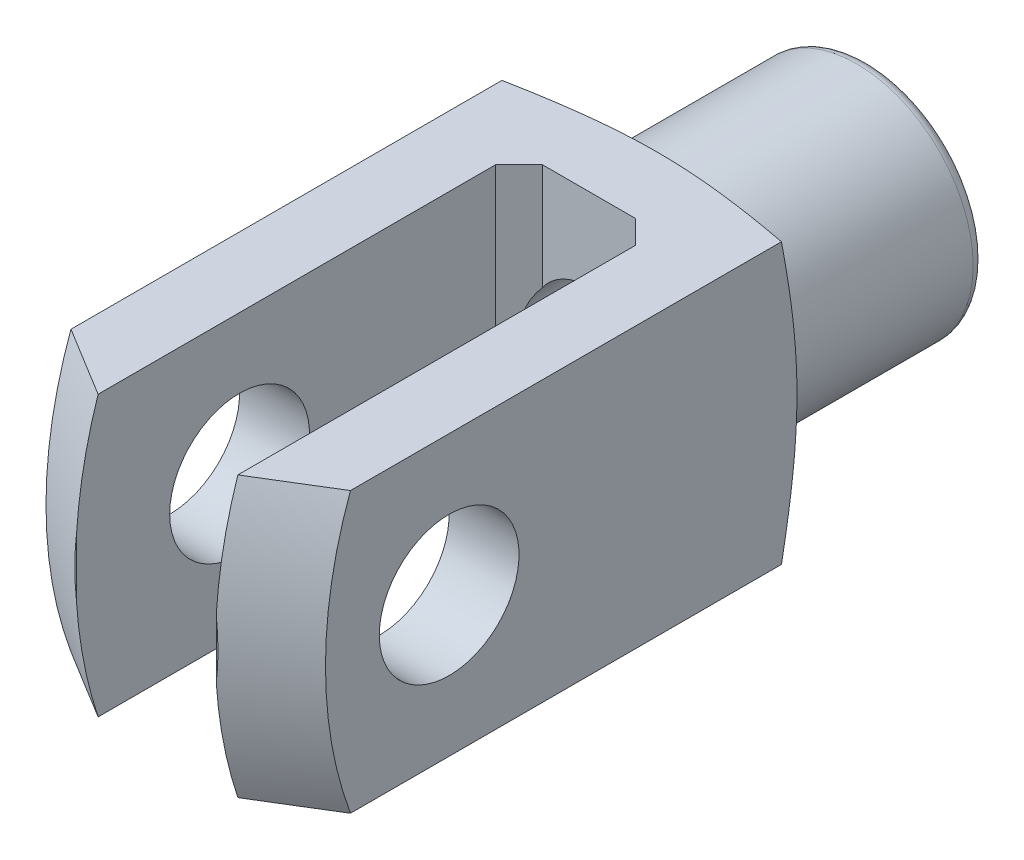
SolidWorks part; units mm, degrees
ref_plane "Front Plane" through (0, 0, 0) normal (0, 0, 1) x (1, 0, 0)
ref_plane "Top Plane" through (0, 0, 0) normal (0, 1, 0) x (1, 0, 0)
ref_plane "Right Plane" through (0, 0, 0) normal (1, 0, 0) x (0, 0, -1)
ref_plane "Plane1" through (0, 0, 0) normal (1, 0, 0) x (0, 0, -1)
sketch "Sketch1" plane through (0, 0, 0) normal (1, 0, 0) x (0, 0, -1)
  line L0 (-7, 0) -> (-7, 12)
  line L1 (-7, 12) -> (13.3253, 12)
  line L2 (13.3253, 12) -> (15, 5.75)
  line L3 (15.75, 5) -> (23.5, 5)
  line L4 (24, 4.5) -> (24, 0)
  line L5 (24, 0) -> (-7, 0)
  line L6 (24, 0) -> (-7, 0) construction
  arc A0 (15, 5.75) -> (15.75, 5) centre (15.75, 5.75) ccw
  arc A1 (23.5, 5) -> (24, 4.5) centre (23.5, 4.5) cw
revolve "Revolve1" add sketch "Sketch1" angle 360 about L6 reverse direction yes
ref_plane "Plane2" through (0, 0, 0) normal (0, 1, 0) x (1, 0, 0)
sketch "Sketch2" plane through (0, 0, 0) normal (0, 1, 0) x (1, 0, 0)
  line L0 (-3, 11) -> (-3, -8)
  line L1 (-3, -8) -> (3, -8)
  line L2 (3, -8) -> (3, 11)
  line L3 (3, 11) -> (2, 12)
  line L4 (2, 12) -> (-2, 12)
  line L5 (-2, 12) -> (-3, 11)
extrude "Cut-Extrude1" cut sketch "Sketch2" against normal blind 13 and the other way blind 13
ref_plane "Plane3" through (0, 0, 0) normal (1, 0, 0) x (0, 0, -1)
sketch "Sketch3" plane through (0, 0, 0) normal (1, 0, 0) x (0, 0, -1)
  line L0 (-20, -18) -> (24, -18)
  line L1 (24, -18) -> (24, -6)
  line L2 (24, -6) -> (-8, -6)
  line L3 (-8, -6) -> (-8, 6)
  line L4 (-8, 6) -> (24, 6)
  line L5 (24, 6) -> (24, 18)
  line L6 (24, 18) -> (-20, 18)
  line L7 (-20, 18) -> (-20, -18)
extrude "Cut-Extrude2" cut sketch "Sketch3" against normal blind 13 and the other way blind 13
ref_plane "Plane4" through (0, 0, 0) normal (0, 1, 0) x (1, 0, 0)
sketch "Sketch4" plane through (0, 0, 0) normal (0, 1, 0) x (1, 0, 0)
  line L0 (-18, -20) -> (18, -20)
  line L1 (18, -20) -> (18, 24)
  line L2 (18, 24) -> (6, 24)
  line L3 (6, 24) -> (6, -8)
  line L4 (6, -8) -> (-6, -8)
  line L5 (-6, -8) -> (-6, 24)
  line L6 (-6, 24) -> (-18, 24)
  line L7 (-18, 24) -> (-18, -20)
extrude "Cut-Extrude3" cut sketch "Sketch4" against normal blind 13 and the other way blind 13
ref_plane "Plane5" through (0, 0, 0) normal (0, 0, 1) x (1, 0, 0)
sketch "Sketch5" plane through (0, 0, 0) normal (0, 0, 1) x (1, 0, 0)
  line L0 (-8.1, 0) -> (-8.1, 3)
  line L1 (-8.1, 3) -> (8.1, 3)
  line L2 (8.1, 3) -> (8.1, 0)
  line L3 (8.1, 0) -> (-8.1, 0)
  line L4 (8.1, 0) -> (-8.1, 0) construction
revolve "Cut-Revolve1" cut sketch "Sketch5" angle 360 about L4 reverse direction yes
ref_plane "Plane6" through (0, 0, 0) normal (1, 0, 0) x (0, 0, -1)
sketch "Sketch6" plane through (0, 0, 0) normal (1, 0, 0) x (0, 0, -1)
  line L0 (10.9, 0) -> (10.9, 2.4585)
  line L1 (10.9, 2.4585) -> (23.5585, 2.4585)
  line L2 (23.5585, 2.4585) -> (24.1, 3)
  line L3 (24.1, 3) -> (24.1, 0)
  line L4 (24.1, 0) -> (10.9, 0)
  line L5 (24.1, 0) -> (10.9, 0) construction
revolve "Cut-Revolve2" cut sketch "Sketch6" angle 360 about L5 reverse direction yes
cosmetic thread "Cosmetic Thread1" parameters "D1"=10.7, "D2"=6
ref_plane "Plane7" through (0, 0, 0) normal (0, 1, 0) x (1, 0, 0)
sketch "Sketch7" plane through (0, 0, 0) normal (0, 1, 0) x (1, 0, 0)
  line L0 (-7, -18.5893) -> (0, -22.6307)
  line L1 (0, -22.6307) -> (7, -18.5893)
  line L2 (7, -18.5893) -> (7, -4.7329)
  line L3 (7, -4.7329) -> (0, -8.7743)
  line L4 (0, -8.7743) -> (-7, -4.7329)
  line L5 (-7, -4.7329) -> (-7, -18.5893)
  line L6 (-7, 12) -> (7, 12) construction
revolve "Cut-Revolve3" cut sketch "Sketch7" angle 90 about L6 other way angle 90 reverse direction yes
